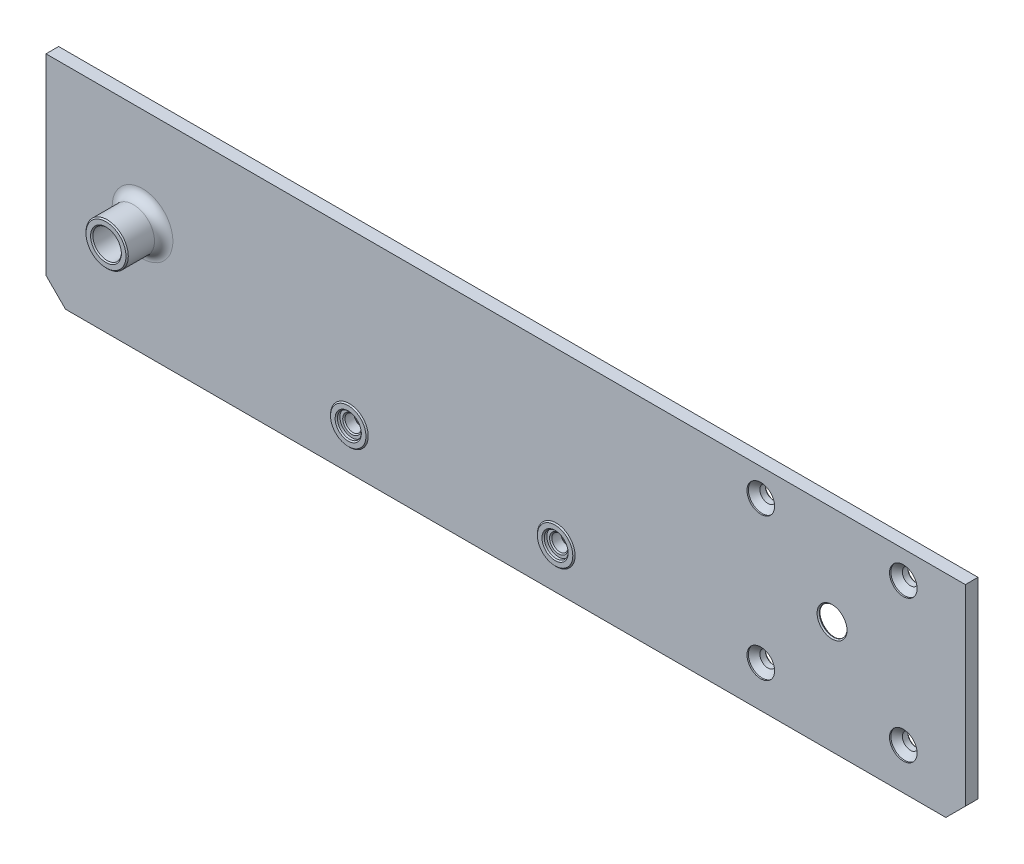
SolidWorks part; units mm, degrees
ref_plane "Front Plane" through (0, 0, 0) normal (0, 0, 1) x (1, 0, 0)
ref_plane "Top Plane" through (0, 0, 0) normal (0, 1, 0) x (1, 0, 0)
ref_plane "Right Plane" through (0, 0, 0) normal (1, 0, 0) x (0, 0, -1)
sketch "Sketch1" plane through (0, 0, 0) normal (0, 0, 1) x (1, 0, 0)
  line L0 (-171, 21.5) -> (29, 21.5)
  line L1 (29, 21.5) -> (29, -20.2574)
  line L2 (29, -20.2574) -> (24.7574, -24.5)
  line L3 (24.7574, -24.5) -> (-166.7574, -24.5)
  line L4 (-166.7574, -24.5) -> (-171, -20.2574)
  line L5 (-171, -20.2574) -> (-171, 21.5)
  line L6 (-14.5858, 21) -> (14.5858, 21) construction
  line L7 (21, 14.5858) -> (21, -14.5858) construction
  line L8 (14.5858, -21) -> (-14.5858, -21) construction
  circle A0 centre (15.5, 15.5) radius 1.75
  circle A1 centre (-15.5, 15.5) radius 1.75
  circle A2 centre (15.5, -15.5) radius 1.75
  circle A3 centre (-15.5, -15.5) radius 1.75
  circle A4 centre (0, 0) radius 3
  dimension "D1" = 3.5
  dimension "D8" = 6
  dimension "D2" = 0.5
  dimension "D3" = 8
  dimension "D4" = 135
  dimension "D5" = 6
  dimension "D6" = 3.5
  dimension "D7" = 200
extrude "Boss-Extrude1" add sketch "Sketch1" along normal blind 3
sketch "Sketch2" plane through (0, 0, 0) normal (0, 0, -1) x (-1, 0, 0)
  circle A2 centre (0, 0) radius 11.45
  circle A3 centre (0, 0) radius 11.45
  dimension "D1" = 0.2
extrude "Cut-Extrude1" cut sketch "Sketch2" against normal blind 2.4
sketch "Sketch3" plane through (0, 0, 3) normal (0, 0, 1) x (1, 0, 0)
  line L0 (15.5, -15.5) -> (-15.5, -15.5) construction
  circle A0 centre (-60, -15.5) radius 1.75
  circle A1 centre (-105, -15.5) radius 1.75
  point P9 (0, 0)
  dimension "D2" = 3.5
  dimension "D1" = 60
  dimension "D3" = 45
extrude "Cut-Extrude2" cut sketch "Sketch3" against normal up to next
sketch "Sketch4" plane through (0, 0, 3) normal (0, 0, 1) x (1, 0, 0)
  circle A0 centre (-60, -15.5) radius 2.6
  circle A1 centre (-105, -15.5) radius 2.6
  dimension "D1" = 5.2
extrude "Cut-Extrude3" cut sketch "Sketch4" against normal blind 0.55
sketch "Sketch5" plane through (0, 0, 3) normal (0, 0, 1) x (1, 0, 0)
  circle A0 centre (-150, 0) radius 3.1
  point P2 (0, 0)
  dimension "D1" = 6.2
  dimension "D2" = 150
extrude "Cut-Extrude4" cut sketch "Sketch5" against normal up to next
sketch "Sketch6" plane through (0, 0, 3) normal (0, 0, 1) x (1, 0, 0)
  circle A0 centre (-150, 0) radius 3.1 construction
  circle A1 centre (-150, 0) radius 3.1
  circle A2 centre (-150, 0) radius 4.6
  point P4 (-150, -3.1)
  point P5 (-150, -4.6)
  dimension "D1" = 1.5
extrude "Boss-Extrude2" add sketch "Sketch6" along normal blind 7.95
sketch "Sketch7" plane through (0, 0, 3) normal (0, 0, 1) x (1, 0, 0)
  circle A0 centre (-60, -15.5) radius 2.6 construction
  circle A1 centre (-105, -15.5) radius 2.6 construction
  circle A2 centre (-60, -15.5) radius 2.6
  circle A3 centre (-105, -15.5) radius 2.6
  circle A4 centre (-60, -15.5) radius 3.6
  circle A5 centre (-105, -15.5) radius 3.6
  point P8 (-60, -18.1)
  point P9 (-60, -19.1)
  dimension "D1" = 1
extrude "Boss-Extrude3" add sketch "Sketch7" along normal mid plane 0.5
hole_wizard "CSK for M3 Flat Head Machine Screw1" positions "Sketch8" profile "Sketch9" countersink size "M3" standard "ANSI Metric" end condition through all
sketch "Sketch8" plane through (0, 0, 3) normal (0, 0, 1) x (1, 0, 0)
  point P0 (-15.5, 15.5)
  point P3 (15.5, 15.5)
  point P6 (15.5, -15.5)
  point P9 (-15.5, -15.5)
sketch "Sketch9" plane through (-15.5, 15.5, 3) normal (1, 0, 0) x (0, -1, 0)
  line L0 (0, 0) -> (0, 3)
  line L1 (0, 3) -> (1.75, 3)
  line L2 (1.75, 3) -> (1.75, 1.55)
  line L3 (1.75, 1.55) -> (3, 0.3)
  line L4 (3, 0.3) -> (3, 0)
  line L6 (3, 0) -> (0, 0)
  line L7 (-1.75, 1.55) -> (-3, 0.3) construction
  line L11 (0, -6.35) -> (0, 107.95) construction
  dimension "Thru Hole Dia." = 3.5
  dimension "Thru Hole Depth" = 3
  dimension "C'Sink Dia." = 6
  dimension "C'Sink Angle" = 90
  dimension "Head Clearance" = 0.3
fillet "Fillet1" radius 2 1 edges at (-145.4, 0, 3)
chamfer "Chamfer1" distance 0.5 angle 45 2 edges at (-63.6, -15.5, 3) (-108.6, -15.5, 3)
chamfer "Chamfer2" distance 0.25 angle 45 23 edges at (-11.45, 0, 2.4) (-3, 0, 2.4) (-61.75, -15.5, 0) (-106.75, -15.5, 0) (-11.45, 0, 0) (-13.75, -15.5, 0) (-13.75, 15.5, 0) (-71, 21.5, 0) (-171, 0.6213, 0) (-168.8787, -22.3787, 0) (-71, -24.5, 0) (26.8787, -22.3787, 0) (29, 0.6213, 0) (17.25, 15.5, 0) (17.25, -15.5, 0) (-146.9, 0, 10.95) (-145.4, 0, 10.95) (3, 0, 3) (-58.25, -15.5, 2.45) (-103.25, -15.5, 2.45) (-57.4, -15.5, 3.25) (-102.4, -15.5, 3.25) (-153.1, 0, 0)
